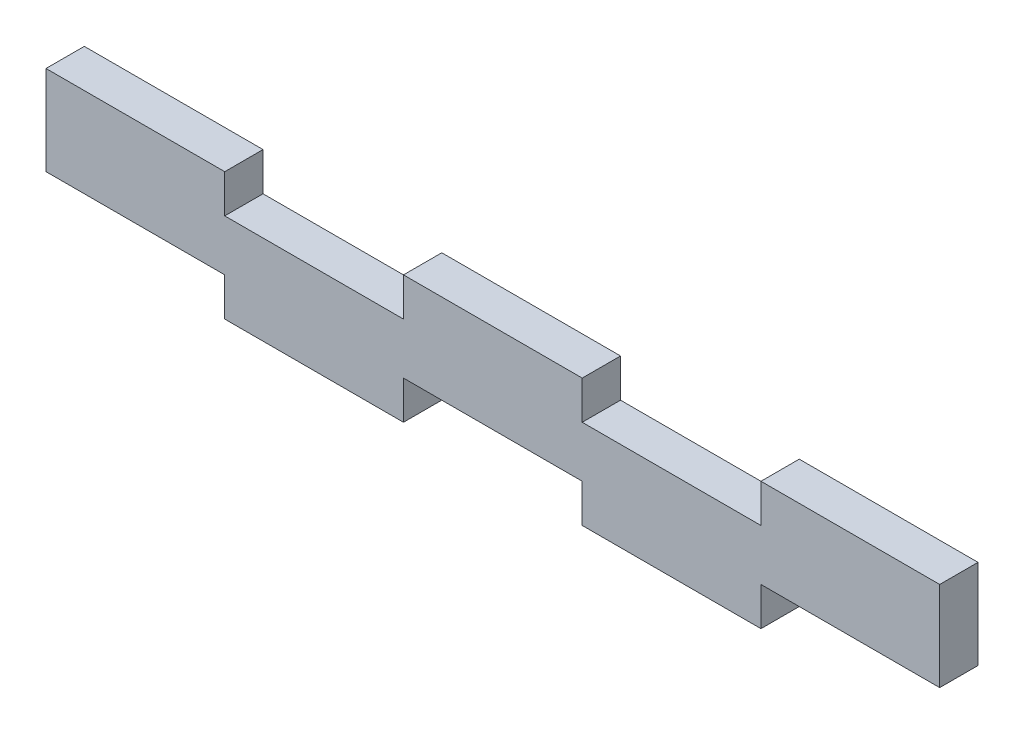
SolidWorks part; units mm, degrees
ref_plane "Front Plane" through (0, 0, 0) normal (0, 0, 1) x (1, 0, 0)
ref_plane "Top Plane" through (0, 0, 0) normal (0, 1, 0) x (1, 0, 0)
ref_plane "Right Plane" through (0, 0, 0) normal (1, 0, 0) x (0, 0, -1)
sketch "Sketch1" plane through (0, 0, 0) normal (0, 0, 1) x (1, 0, 0)
  line L1 (-7, 0) -> (7, 0)
  line L2 (7, 0) -> (7, -3)
  line L3 (-21, -3) -> (-7, -3)
  line L4 (21, -3) -> (21, 0)
  line L5 (21, 0) -> (35, 0)
  line L6 (35, 0) -> (35, 7)
  line L7 (35, 7) -> (21, 7)
  line L8 (21, 7) -> (21, 4)
  line L9 (-21, 4) -> (-7, 4)
  line L10 (7, 4) -> (7, 7)
  line L11 (7, 7) -> (-7, 7)
  line L12 (7, 4) -> (21, 4)
  line L13 (-7, 4) -> (-7, 7)
  line L14 (-21, 7) -> (-21, 4)
  line L15 (-35, 7) -> (-21, 7)
  line L16 (-35, 0) -> (-35, 7)
  line L17 (-21, 0) -> (-35, 0)
  line L18 (-21, -3) -> (-21, 0)
  line L19 (7, -3) -> (21, -3)
  line L20 (-7, 0) -> (-7, -3)
  dimension "D2" = 14
  dimension "D3" = 14
  dimension "D4" = 7
  dimension "D5" = 14
  dimension "D6" = 14
  dimension "D7" = 7
  dimension "D8" = 3
  dimension "D9" = 14
  dimension "D10" = 3
  dimension "D11" = 3
  dimension "D12" = 14
extrude "Boss-Extrude1" add sketch "Sketch1" along normal blind 3
